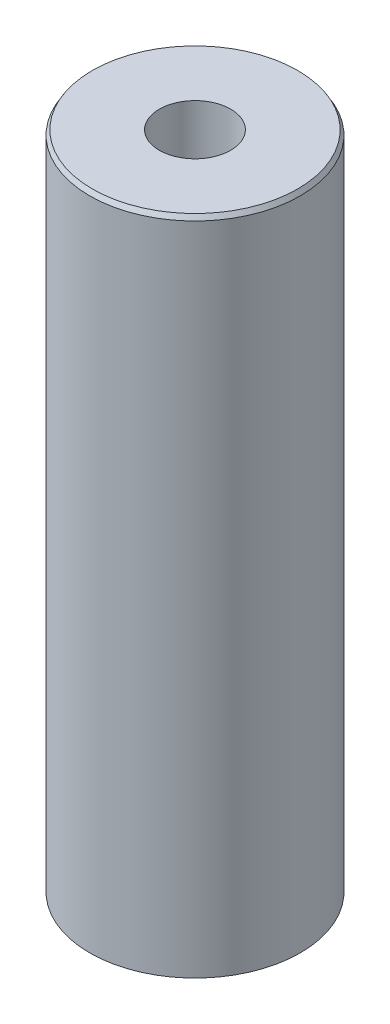
SolidWorks part; units mm, degrees
ref_plane "Front Plane" through (0, 0, 0) normal (0, 0, 1) x (1, 0, 0)
ref_plane "Top Plane" through (0, 0, 0) normal (0, 1, 0) x (1, 0, 0)
ref_plane "Right Plane" through (0, 0, 0) normal (1, 0, 0) x (0, 0, -1)
sketch "Sketch1" plane through (0, 0, 0) normal (0, 1, 0) x (1, 0, 0)
  circle A0 centre (0, 0) radius 57.5
  dimension "SHAFT_OD" = 115
extrude "Boss-Extrude1" add sketch "Sketch1" along normal blind 361.8982
sketch "Sketch2" plane through (0, 0, 0) normal (0, 1, 0) x (1, 0, 0)
  circle A0 centre (0, 0) radius 19.4807
  dimension "BORE_D" = 38.9614
extrude "Cut-Extrude1" cut sketch "Sketch2" along normal through all
chamfer "Chamfer1" distance 2.5236 angle 30 2 edges at (0, 361.8982, 57.5) (0, 0, 57.5) first distance on face at (0, 361.8982, 57.5) first distance on face at (0, 0, 19.4807)
